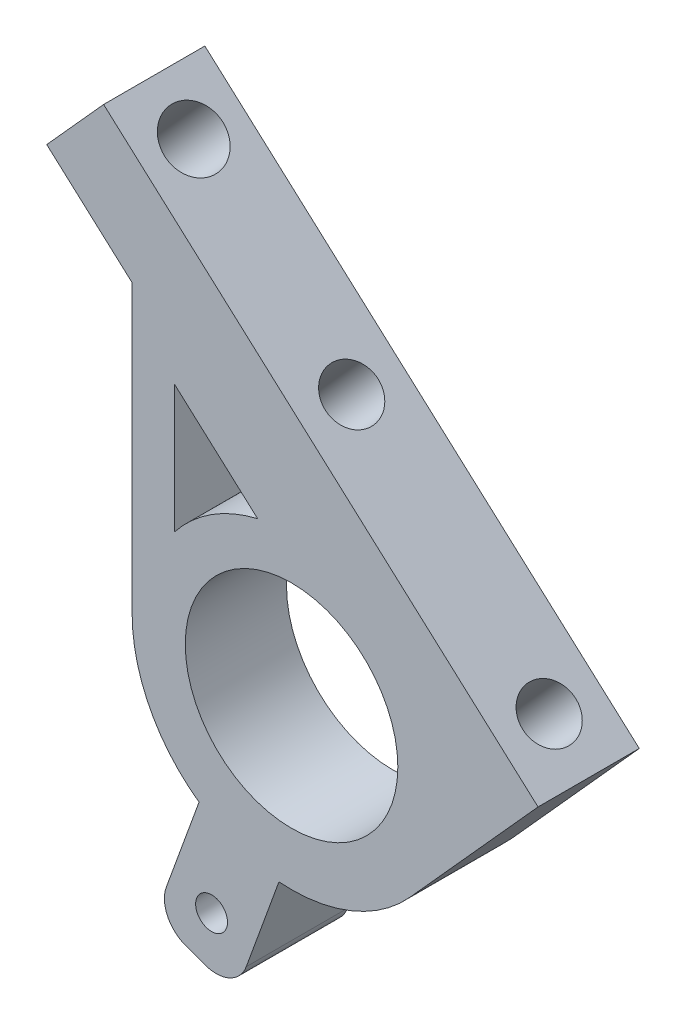
SolidWorks part; units mm, degrees
material "6061 Alloy"
ref_plane "Front Plane" through (0, 0, 0) normal (0, 0, 1) x (1, 0, 0)
ref_plane "Top Plane" through (0, 0, 0) normal (0, 1, 0) x (1, 0, 0)
ref_plane "Right Plane" through (0, 0, 0) normal (1, 0, 0) x (0, 0, -1)
sketch "Sketch1" plane through (0, 0, 0) normal (0, 0, 1) x (1, 0, 0)
  line L0 (-17.6814, 40.1418) -> (21.9261, 40.1418) construction
  line L1 (-15, 0) -> (-15, 26.9624)
  line L2 (-15, 26.9624) -> (-23.0345, 34.1967)
  line L3 (-23.0345, 34.1967) -> (-17.6814, 40.1418)
  line L4 (-17.6814, 40.1418) -> (23.1915, 3.3396)
  line L5 (23.1915, 3.3396) -> (17.8385, -2.6055)
  line L10 (17.8385, -2.6055) -> (11.1472, -10.037)
  line L11 (-15, 26.9624) -> (17.8385, -2.6055) construction
  circle A0 centre (0, 0) radius 10
  arc A1 (-15, 0) -> (11.1472, -10.037) centre (0, 0) ccw
  dimension "D3" = 20
  dimension "D4" = 5
  dimension "D1" = 42
  dimension "D2" = 8
  dimension "D7" = 55
extrude "3/8" add sketch "Sketch1" along normal blind 9.525
sketch "Sketch2" plane through (0, 0, 0) normal (0, 0, 1) x (1, 0, 0)
  line L0 (0, 0) -> (0, -7.8768) construction
  line L1 (-8.7033, -12.2169) -> (-1.1858, -14.9531)
  line L2 (-8.7033, -12.2169) -> (-12.8075, -23.4932)
  line L3 (-12.8075, -23.4932) -> (-5.29, -26.2294)
  line L4 (-1.1858, -14.9531) -> (-5.29, -26.2294)
  line L5 (-9.0488, -24.8613) -> (-4.9445, -13.585) construction
  line L6 (-10.7554, -17.8551) -> (-3.2379, -20.5912) construction
  arc A0 (-15, 0) -> (11.1472, -10.037) centre (0, 0) ccw construction
  point P360 (-6.9966, -19.2231)
  dimension "D1" = 12
  dimension "D2" = 8
  dimension "D3" = 110
extrude "Boss-Extrude2" add sketch "Sketch2" along normal up to surface (9.525 mm away) up to face at (-6.6377, 14.2697, 9.525)
sketch "Sketch3" plane through (0, 0, 9.525) normal (0, 0, 1) x (1, 0, 0)
  line L0 (0, 0) -> (-9.0488, -24.8613) construction
  line L1 (-12.8075, -23.4932) -> (-5.29, -26.2294) construction
  circle A0 centre (-7.5244, -20.6732) radius 1.5
  dimension "D2" = 3
  dimension "D1" = 22
extrude "Cut-Extrude1" cut sketch "Sketch3" against normal up to surface (9.525 mm away) up to face at (-6.5272, 1.5509, 0)
fillet "Fillet1" radius 3 2 edges at (-5.29, -26.2294, 4.7625) (-12.8075, -23.4932, 4.7625)
sketch "Sketch4" plane through (12.0444, 13.3766, 0) normal (0.6691, 0.7431, 0) x (0.7431, -0.6691, 0)
  line L0 (-40, -4.7625) -> (15, -4.7625) construction
  line L1 (-40, -9.525) -> (-40, 0) construction
  line L2 (15, -9.525) -> (15, 0) construction
  circle A0 centre (-35, -4.7625) radius 2.75
  dimension "D2" = 5.5
  dimension "D1" = 5
extrude "M5_through" cut sketch "Sketch4" against normal up to surface (8 mm away) up to face at (-19.0172, 30.5795, 4.7625)
sketch "Sketch5" plane through (12.0444, 13.3766, 0) normal (0.6691, 0.7431, 0) x (0.7431, -0.6691, 0)
  line L0 (-35, -4.7625) -> (10, -4.7625) construction
  circle A0 centre (-15, -4.7625) radius 2.5
  circle A1 centre (10, -4.7625) radius 2.5
  dimension "D1" = 5
  dimension "D2" = 20
  dimension "D3" = 45
extrude "M5_DRILL" cut sketch "Sketch5" against normal blind 8
sketch "Sketch6" plane through (0, 0, 9.525) normal (0, 0, 1) x (1, 0, 0)
  line L0 (-11, 20.6695) -> (-11, 8.6603)
  line L1 (-11, 20.6695) -> (-3.185, 13.6329)
  line L2 (23.1915, 3.3396) -> (-17.6814, 40.1418) construction
  line L3 (-15, 26.9624) -> (-15, 0) construction
  arc A0 (-11, 8.6603) -> (-3.185, 13.6329) centre (0, 0) cw
  circle A1 centre (0, 0) radius 10 construction
  dimension "D3" = 4
  dimension "D1" = 10
  dimension "D2" = 4
extrude "Cut-Extrude4" cut sketch "Sketch6" against normal up to vertex (9.525 mm away) up to point (-17.6814, 40.1418, 0)
